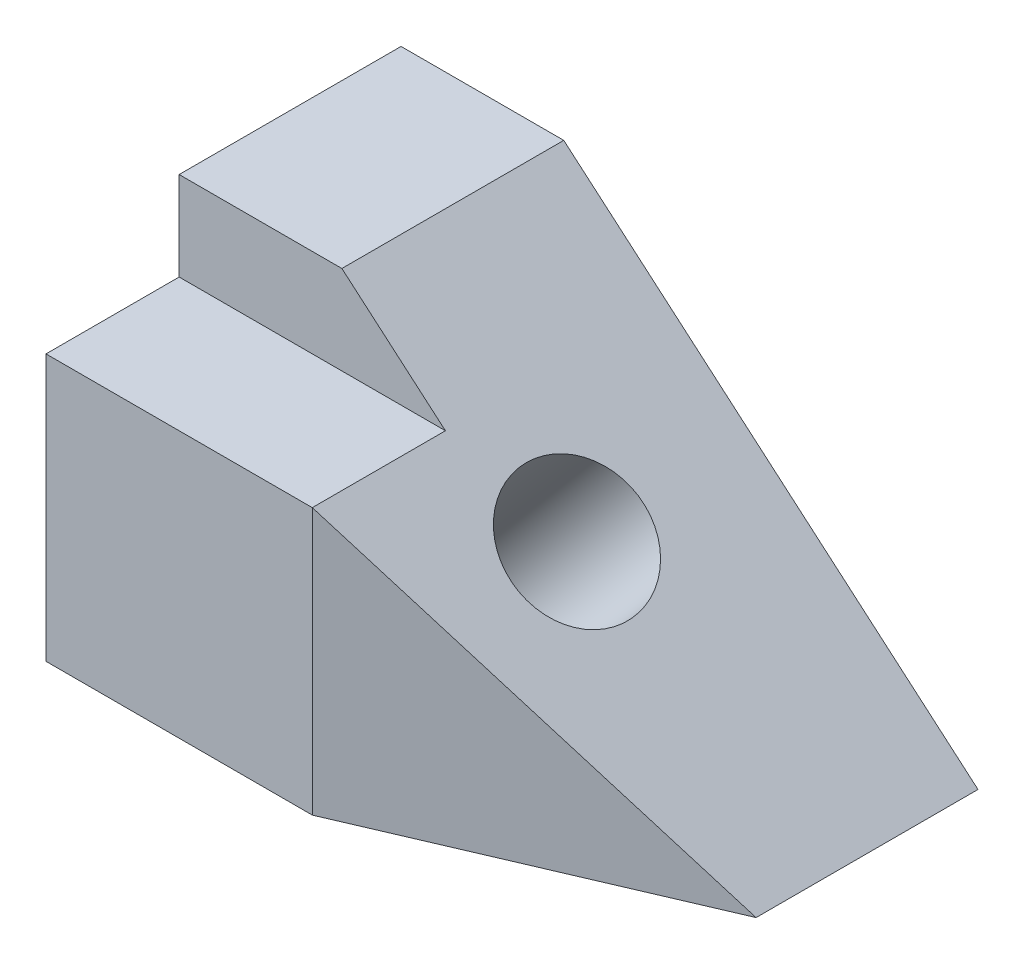
SolidWorks part; units mm, degrees
ref_plane "Front Plane" through (0, 0, 0) normal (0, 0, 1) x (1, 0, 0)
ref_plane "Top Plane" through (0, 0, 0) normal (0, 1, 0) x (1, 0, 0)
ref_plane "Right Plane" through (0, 0, 0) normal (1, 0, 0) x (0, 0, -1)
sketch "Sketch1" plane through (0, 0, 0) normal (0, 0, 1) x (1, 0, 0)
  line L0 (-64.6286, 106.1714) -> (-64.6286, 26.1714)
  line L1 (-64.6286, 26.1714) -> (65.3714, 26.1714)
  line L2 (65.3714, 26.1714) -> (-27.9619, 106.1714)
  line L3 (-27.9619, 106.1714) -> (-64.6286, 106.1714)
  line L4 (-64.6286, 86.1714) -> (-4.6286, 86.1714)
  line L5 (-4.6286, 86.1714) -> (-4.6286, 26.1714)
  dimension "D1" = 130
  dimension "D2" = 80
  dimension "D3" = 60
extrude "Boss-Extrude1" add sketch "Sketch1" against normal blind 50 contours L0 L4 L2 L3 | L5 L4 L0 L1 | L2 L5 L1 region at (-39.9926, 95.3668, 0) region at (-34.6286, 56.1714, 0) region at (18.7048, 46.1714, 0)
extrude "Boss-Extrude2" add sketch "Sketch1<4>" along normal blind 30 contours L5 L4 L0 L1 | L2 L5 L1 region at (-34.6286, 56.1714, 0) region at (18.7048, 46.1714, 0)
sketch "Sketch1<4>" plane through (0, 0, 0) normal (0, 0, 1) x (1, 0, 0) same geometry as "Sketch1"
sketch "Sketch3" plane through (40.6185, 47.3882, 0) normal (0.6508, 0.7593, 0) x (0.7593, -0.6508, 0)
  circle A0 centre (-33.7257, 10) radius 15
  point P2 (0, 0)
  point P3 (0, 0)
  point P6 (32.6015, 50)
  dimension "D1" = 30
  dimension "D2" = 40
  dimension "D3" = 56.6
extrude "Cut-Extrude1" cut sketch "Sketch3" against normal blind 30
sketch "Sketch4" plane through (0, 86.1714, 0) normal (0, 1, 0) x (1, 0, 0)
  line L1 (65.3714, -30) -> (-4.6286, -30)
  line L2 (-4.6286, -30) -> (-4.6286, 0) construction
  line L4 (-4.6286, -30) -> (65.3714, 0)
  line L5 (65.3714, 50) -> (65.3714, -30) construction
  line L6 (65.3714, 0) -> (65.3714, -30)
extrude "Cut-Extrude3" cut sketch "Sketch4" against normal up to next contours L6 L1 L4
extrude "Cut-Extrude4" cut sketch "Sketch3<3>" against normal up to next
sketch "Sketch3<3>" plane through (40.6185, 47.3882, 0) normal (0.6508, 0.7593, 0) x (0.7593, -0.6508, 0) same geometry as "Sketch3"
